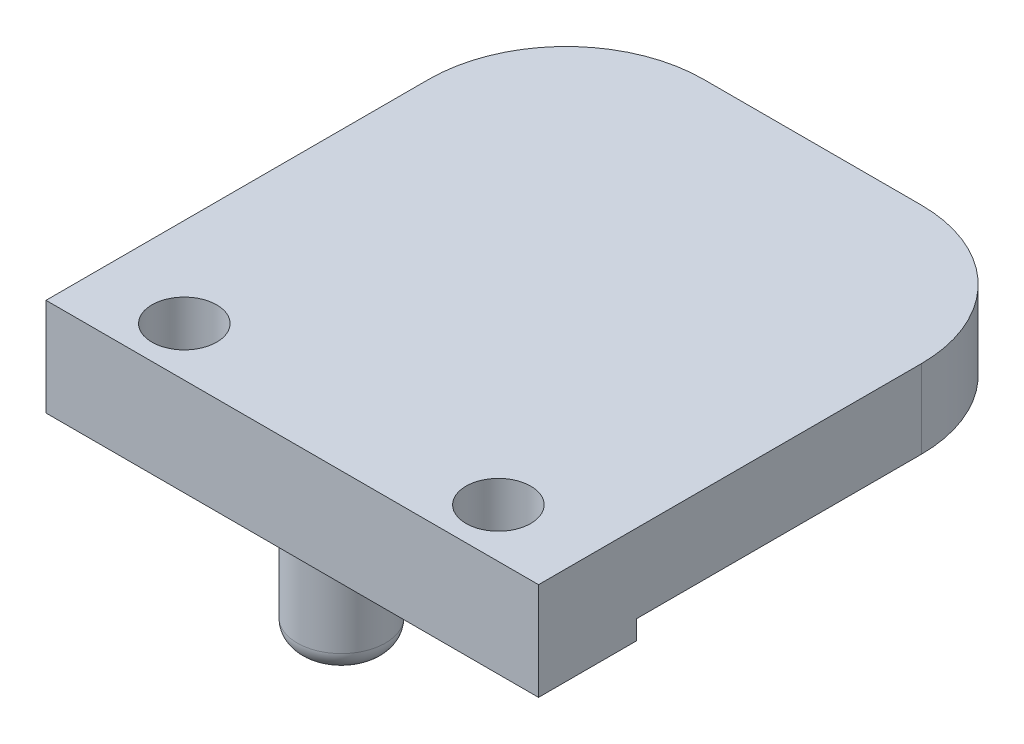
SolidWorks part; units mm, degrees
ref_plane "Front Plane" through (0, 0, 0) normal (0, 0, 1) x (1, 0, 0)
ref_plane "Top Plane" through (0, 0, 0) normal (0, 1, 0) x (1, 0, 0)
ref_plane "Right Plane" through (0, 0, 0) normal (1, 0, 0) x (0, 0, -1)
sketch "Sketch4" plane through (0, 0, 0) normal (0, 0, 1) x (1, 0, 0)
  line L1 (-6.23, -9.975) -> (6.23, -9.975)
  line L2 (-6.23, -9.975) -> (-6.23, 7.275)
  line L3 (-6.23, 7.275) -> (6.23, 7.275)
  line L4 (6.23, -9.975) -> (6.23, 7.275)
  point P4 (0, 7.275)
  dimension "D1" = 12.46
  dimension "D2" = 17.25
  dimension "D3" = 9.975
extrude "Boss-Extrude3" add sketch "Sketch4" along normal blind 6
sketch "Sketch8" plane through (0, -9.975, 0) normal (0, -1, 0) x (-1, 0, 0)
  circle A0 centre (0, -23.55) radius 12.5468
  circle A1 centre (0, -23.55) radius 11.15
  dimension "D1" = 22.3
  dimension "D2" = 23.55
extrude "Boss-Extrude6" add sketch "Sketch8" along normal blind 8.3 and the other way up to surface (17.25 mm away) other way up to face at (0, 7.275, 3)
sketch "Sketch5" plane through (0, 7.275, 0) normal (0, 1, 0) x (1, 0, 0)
  line L8 (12.5468, -23.55) -> (12.5468, 0)
  line L9 (12.5468, 0) -> (6.23, 0)
  line L10 (-12.5468, -23.55) -> (-12.5468, 0)
  line L11 (-12.5468, 0) -> (-6.23, 0)
  line L12 (-6.23, 0) -> (-6.23, -29.7)
  line L14 (6.23, -29.7) -> (6.23, 0)
  line L15 (-6.23, -29.7) -> (6.23, -29.7)
  line L16 (6.23, -6) -> (-6.23, -6) construction
  circle A0 centre (0, -23.55) radius 12.5468 construction
  arc A1 (-12.5468, -23.55) -> (12.5468, -23.55) centre (0, -23.55) ccw
  dimension "D1" = 23.7
  dimension "D2" = 23.55
extrude "Boss-Extrude4" add sketch "Sketch5" against normal up to surface (17.25 mm away) up to face at (0, -9.975, 3)
sketch "Sketch6" plane through (0, 7.275, 0) normal (0, 1, 0) x (1, 0, 0)
  line L0 (6.23, -6) -> (-6.23, -6) construction
  line L3 (6.23, -29.7) -> (-6.23, -29.7) construction
  circle A0 centre (0, -3.6) radius 0.75
  circle A1 centre (0, -32.1) radius 0.75
  dimension "D1" = 1.5
  dimension "D3" = 1.5
  dimension "D2" = 2.4
  dimension "D4" = 2.4
extrude "Cut-Extrude1" cut sketch "Sketch6" against normal blind 5
chamfer "Chamfer1" distance 0.5 angle 60 2 edges at (0, 7.275, 4.35) (0, 7.275, 32.85) first distance on face at (0, 7.275, 4.35)
sketch "Sketch10" plane through (0, 7.275, 0) normal (0, 1, 0) x (1, 0, 0)
  line L1 (-6.23, -6) -> (6.23, -6)
  line L2 (-6.23, -6) -> (-6.23, -29.7)
  line L3 (-6.23, -29.7) -> (6.23, -29.7)
  line L4 (6.23, -6) -> (6.23, -29.7)
extrude "Cut-Extrude3" cut sketch "Sketch10" against normal up to surface (17.25 mm away) up to face at (0, -9.975, 10.3399)
ref_plane "Plane1" through (0, 0, 36.0968) normal (0, 0, 1) x (1, 0, 0)
sketch "Sketch13" plane through (0, -18.275, 0) normal (0, -1, 0) x (1, 0, 0)
  line L0 (-12.5468, 23.55) -> (-12.5468, 0)
  line L1 (-12.5468, 0) -> (12.5468, 0)
  line L2 (12.5468, 0) -> (12.5468, 23.55)
  arc A0 (-12.5468, 23.55) -> (12.5468, 23.55) centre (0, 23.55) ccw
  point P3 (0, 0)
extrude "Boss-Extrude7" add sketch "Sketch13" against normal up to surface (8.3 mm away) up to face at (0, -9.975, 10.3399)
sketch "Sketch15" plane through (0, 7.275, 0) normal (0, 1, 0) x (1, 0, 0)
  line L0 (-12.5468, 0) -> (12.5468, 0)
  line L1 (12.5468, 0) -> (12.5468, -23.55)
  line L2 (-12.5468, 0) -> (-12.5468, -23.55)
  line L3 (6.23, -6) -> (6.23, -29.7) construction
  line L4 (-6.23, -0.8) -> (6.23, -0.8)
  line L5 (-6.23, -0.8) -> (-6.23, -33)
  line L6 (-4.73, -34.5) -> (4.73, -34.5)
  line L7 (6.23, -0.8) -> (6.23, -33)
  arc A0 (-12.5468, -23.55) -> (12.5468, -23.55) centre (0, -23.55) ccw
  circle A1 centre (0, -3.6) radius 0.75 construction
  arc A2 (4.73, -34.5) -> (6.23, -33) centre (4.73, -33) ccw
  arc A3 (-6.23, -33) -> (-4.73, -34.5) centre (-4.73, -33) ccw
  point P15 (0, -0.8)
  dimension "D1" = 0.8
  dimension "D3" = 1.5
  dimension "D2" = 2.8
  dimension "D4" = 0
  dimension "D5" = 34.5
extrude "Boss-Extrude9" add sketch "Sketch15" along normal blind 10
sketch "Sketch20" plane through (0, -18.275, 0) normal (0, -1, 0) x (1, 0, 0)
  circle A0 centre (0, 23.55) radius 7.15
  circle A1 centre (0, 23.55) radius 11.15
  circle A2 centre (0, 23.55) radius 11.15 construction
  dimension "D1" = 14.3
extrude "Boss-Extrude11" add sketch "Sketch20" against normal up to surface (8.3 mm away) up to face at (0, -9.975, 27.1007)
sketch "Sketch21" plane through (0, -18.275, 0) normal (0, -1, 0) x (1, 0, 0)
  circle A0 centre (0, 23.55) radius 7.15
  circle A1 centre (0, 23.55) radius 10.15
  circle A2 centre (0, 23.55) radius 7.15 construction
  dimension "D1" = 20.3
extrude "Cut-Extrude7" cut sketch "Sketch21" against normal blind 1.3
sketch "Sketch11" plane through (0, 0, 29.7) normal (0, 0, 1) x (1, 0, 0)
  line L1 (-5, -9.975) -> (5, -9.975)
  line L2 (-5, -9.975) -> (-5, -11.975)
  line L3 (-5, -11.975) -> (5, -11.975)
  line L4 (5, -9.975) -> (5, -11.975)
  line L5 (3.6469, -9.975) -> (6.23, -9.975) construction
  point P4 (0, -9.975)
  dimension "D1" = 0
  dimension "D2" = 10
  dimension "D3" = 2
extrude "Cut-Extrude4" cut sketch "Sketch11" against normal up to surface (23.7 mm away) up to face at (0, -1.35, 6)
sketch "Sketch24" plane through (0, -18.275, 0) normal (0, -1, 0) x (1, 0, 0)
  line L0 (6.23, 20.0415) -> (6.23, 6) construction
  line L1 (-6.23, 6) -> (6.23, 6)
  line L2 (-6.23, 6) -> (-6.23, 12)
  line L3 (-6.23, 12) -> (6.23, 12)
  line L4 (6.23, 6) -> (6.23, 12)
  dimension "D1" = 6
extrude "Cut-Extrude8" cut sketch "Sketch24" against normal up to next
sketch "Sketch17" plane through (-12.5468, 4.7282, 0) normal (1, 0, 0) x (0, -1, 0)
  line L0 (26.9782, 26.5) -> (26.9782, 0)
  line L1 (26.9782, 0) -> (-17.5218, 0)
  line L2 (-17.5218, 0) -> (-17.5218, 26.5)
  line L3 (-17.5218, 26.5) -> (-13.5218, 26.5)
  line L4 (-13.5218, 26.5) -> (-13.5218, 5)
  line L5 (-13.5218, 5) -> (22.9782, 5)
  line L6 (22.9782, 5) -> (22.9782, 26.5)
  line L7 (22.9782, 26.5) -> (26.9782, 26.5)
  point P2 (4.7282, 5)
  point P10 (4.7282, 0)
  dimension "D1" = 4
  dimension "D2" = 36.5
  dimension "D3" = 0
  dimension "D4" = 26.5
  dimension "D5" = 5
extrude "Boss-Extrude10" add sketch "Sketch17" along normal up to surface (25.0936 mm away) up to face at (12.5468, -0.5, 11.775)
sketch "Sketch18" plane through (0, -18.25, 0) normal (0, 1, 0) x (0, 0, 1)
  line L0 (-26.5, -12.5468) -> (-26.5, 12.5468) construction
  line L1 (-26.5, 6.2191) -> (-5, 6.2191)
  line L2 (-26.5, 6.2191) -> (-26.5, -6.2191)
  line L3 (-26.5, -6.2191) -> (-5, -6.2191)
  line L4 (-5, 6.2191) -> (-5, -6.2191)
  line L5 (-5, -12.5468) -> (-5, 12.5468) construction
  point P6 (-26.5, 0)
  point P7 (-26.5, 0)
  dimension "D1" = 0
extrude "Cut-Extrude5" cut sketch "Sketch18" against normal blind 2
sketch "Sketch19" plane through (0, -20.25, 0) normal (0, 1, 0) x (0, 0, 1)
  line L0 (-26.5, -12.5468) -> (-26.5, 12.5468) construction
  line L1 (-26.5, 12.5468) -> (-26.5, -12.5468) construction
  circle A0 centre (-20, 0) radius 3.5
  point P8 (-26.5, 0)
  dimension "D1" = 7
  dimension "D2" = 6.5
extrude "Cut-Extrude6" cut sketch "Sketch19" against normal through all both and the other way through all
fillet "Fillet1" radius 7 4 edges at (12.5468, -20.25, -26.5) (-12.5468, -20.25, -26.5) (-12.5468, 20.25, -26.5) (12.5468, 20.25, -26.5)
ref_plane "Plane2" through (0, 0, 0) normal (1, 0, 0) x (0, 0, -1)
ref_plane "Plane3" through (0, -0.5, 0) normal (0, -1, 0) x (-1, 0, 0)
sketch "Sketch22" plane through (0, 22.25, 0) normal (0, 1, 0) x (1, 0, 0)
  circle A0 centre (0, 20) radius 6.5
  dimension "D1" = 13
extrude "Boss-Extrude12" add sketch "Sketch22" against normal blind 5
sketch "Sketch23" plane through (0, 17.25, 0) normal (0, -1, 0) x (1, 0, 0)
  circle A0 centre (0, -20) radius 6.075
  dimension "D1" = 12.15
extrude "Boss-Extrude13" add sketch "Sketch23" along normal blind 5
fillet "Fillet2" radius 1 1 edges at (0, 12.25, -26.075)
sketch "Sketch25" plane through (0, -20.25, 0) normal (0, 1, 0) x (1, 0, 0)
  line L0 (-6.2191, 5) -> (-2.5, 5)
  line L1 (12.5468, 5) -> (-12.5468, 5) construction
  line L2 (-2.5, 5) -> (-3.1585, 20)
  line L3 (-3.1585, 20) -> (-3.4438, 26.5)
  line L4 (-3.4438, 26.5) -> (-6.2191, 26.5)
  line L5 (-6.2191, 26.4676) -> (-6.2191, 5) construction
  line L6 (-6.2191, 26.5) -> (-6.2191, 5)
  line L7 (6.2191, 5) -> (2.5, 5)
  line L8 (2.5, 5) -> (3.1585, 20)
  line L9 (3.1585, 20) -> (3.4438, 26.5)
  line L10 (3.4438, 26.5) -> (6.2191, 26.5)
  line L11 (6.2191, 5) -> (6.2191, 26.4676) construction
  line L12 (6.2191, 26.5) -> (6.2191, 5)
  line L13 (0, -23.6775) -> (0, 23.6775) construction
  line L14 (5.5468, 26.5) -> (-5.5468, 26.5) construction
  circle A0 centre (0, 20) radius 3.5 construction
  dimension "D1" = 5
  dimension "D2" = 2.5
  dimension "D3" = 3.1585
  dimension "D4" = 6.317
  dimension "D5" = 0
  dimension "D6" = 0
extrude "Boss-Extrude15" add sketch "Sketch25" along normal up to surface (2 mm away) up to face at (9.7194, -18.25, -14.2975)
sketch "Sketch26" plane through (0, -22.25, 0) normal (0, -1, 0) x (-1, 0, 0)
  circle A0 centre (0, 10) radius 0.75
  circle A1 centre (0, 20) radius 3.5 construction
  dimension "D1" = 1.5
  dimension "D2" = 10
  dimension "D3" = 0
extrude "Cut-Extrude9" cut sketch "Sketch26" against normal up to next
sketch "Sketch27" plane through (-12.5468, 0, 0) normal (-1, 0, 0) x (0, 0, 1)
  line L0 (36.0968, 17.275) -> (-10.0207, 17.275)
  line L1 (-10.0207, 17.275) -> (-10.0207, 5.3316)
  line L2 (-10.0207, 5.3316) -> (-33.3295, 5.3316)
  line L3 (-33.3295, 5.3316) -> (-33.3295, -27.205)
  line L4 (-33.3295, -27.205) -> (36.0968, -27.205)
  line L5 (36.0968, -27.205) -> (36.0968, 17.275)
extrude "Cut-Extrude10" cut sketch "Sketch27" against normal through all
sketch "Sketch28" plane through (0, 17.275, 0) normal (0, -1, 0) x (1, 0, 0)
  line L0 (0, -2.7363) -> (0, 2.7363) construction
  line L1 (12.5468, 0) -> (-12.5468, 0) construction
  circle A0 centre (-8, -2.5) radius 1.65
  circle A1 centre (8, -2.5) radius 1.65
  point P4 (0, 0)
  point P7 (0, 0)
  point P9 (-22.5738, 2.7042)
  dimension "D1" = 3.3
  dimension "D2" = 3.3
  dimension "D3" = 16
  dimension "D4" = 8
  dimension "D5" = 2.5
extrude "Cut-Extrude11" cut sketch "Sketch28" against normal through all
sketch "Sketch29" plane through (0, 17.275, 0) normal (0, -1, 0) x (1, 0, 0)
  line L0 (0, -2.7363) -> (0, 2.7363) construction
  circle A0 centre (0, -2.5) radius 2.25
  circle A1 centre (-8, -2.5) radius 1.65 construction
  point P4 (0, 0)
  dimension "D2" = 4.5
  dimension "D1" = 0
extrude "Boss-Extrude16" add sketch "Sketch29" along normal blind 5
fillet "Fillet3" radius 1 1 edges at (0, 12.275, -4.75)
